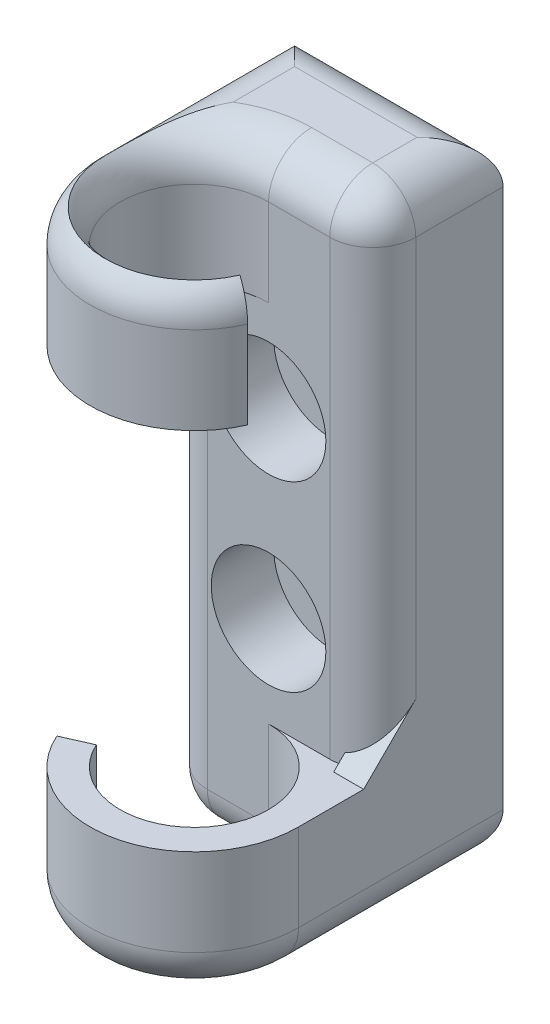
SolidWorks part; units mm, degrees
ref_plane "Front Plane" through (0, 0, 0) normal (1, 0, 0) x (0, 1, 0)
ref_plane "Top Plane" through (0, 0, 0) normal (0, 0, 1) x (0, 1, 0)
ref_plane "Right Plane" through (0, 0, 0) normal (0, 1, 0) x (-1, 0, 0)
sketch "Sketch1" plane through (0, 0, 0) normal (0, 0, 1) x (0, 1, 0)
  line L0 (-10, 0) -> (-12, 0) construction
  line L1 (-10, 2.35) -> (10, 2.35)
  line L2 (-10, 2.35) -> (-10, -2.35)
  line L3 (-10, -2.35) -> (10, -2.35)
  line L4 (10, 2.35) -> (10, -2.35)
  line L5 (-10, 2.35) -> (10, -2.35) construction
  line L6 (-10, -2.35) -> (10, 2.35) construction
  line L7 (-12, 4) -> (12, 4)
  line L8 (-12, 4) -> (-12, -4)
  line L9 (-12, -4) -> (12, -4)
  line L10 (12, 4) -> (12, -4)
  line L11 (0, 2.35) -> (0, 4) construction
  point P0 (0, 0)
  dimension "D1" = 4.7
  dimension "D2" = 20
  dimension "D3" = 2
  dimension "D4" = 8
extrude "Base" add sketch "Sketch1" along normal blind 5 contours L4 L1 L2 L3 | L10 L7 L8 L9 L1 L4 L3 L2 region at (0, 0, 0) region at (-3.747, 0, 0)
sketch "Hook Path" plane through (0, 12, 0) normal (0, 1, 0) x (-1, 0, 0)
  line L0 (2.85, 5) -> (2.85, 7.85)
  line L1 (4, 5) -> (-4, 5) construction
  line L2 (2.85, 7.85) -> (0, 7.85) construction
  line L3 (0, 5) -> (0, 7.85) construction
  line L4 (4, 5) -> (4, 0) construction
  arc A0 (2.85, 7.85) -> (-2.6077, 9) centre (0, 7.85) ccw
  circle A3 centre (0, 7.35) radius 2.35 construction
  point P6 (0, 10.7)
  point P11 (0, 9.7)
  dimension "D2" = 2.85
  dimension "D5" = 1.15
  dimension "D6" = 1
  dimension "D4" = 4.7
  dimension "D1" = 2.85
  dimension "D3" = 4
sketch "Sketch - Hook Base" plane through (0, 0, 5) normal (0, 0, 1) x (1, 0, 0)
  line L1 (-4, 12) -> (-2.85, 12)
  line L2 (-4, 12) -> (-4, 7)
  line L3 (-4, 7) -> (-2.85, 7)
  line L4 (-2.85, 12) -> (-2.85, 7)
  line L5 (-4, 12) -> (4, 12) construction
  line L6 (-4, -12) -> (-4, 12) construction
  dimension "D1" = 1.15
  dimension "D2" = 5
fillet "Base-Fillet" radius 1.65 2 edges at (4, 0, 5) (-4, 0, 5)
extrude "Hook Base" add sketch "Sketch - Hook Base" against normal up to surface (5 mm away) contours L3 L4 L1 L2 up to face at (0, 0, 0)
sweep "Hook" add profiles "Sketch - Hook Base<3>" path "Hook Path"
sketch "Sketch - Hook Base<3>" plane through (0, 0, 5) normal (0, 0, 1) x (1, 0, 0) same geometry as "Sketch - Hook Base"
ref_plane "Plane - Hook Rib" through (-3.425, 0, 0) normal (1, 0, 0) x (0, 1, 0)
ref_point "Top Face Midpoint"
ref_axis "Axis - Top Face Midpoint" through (0, 0, 5) along (0, 0, 1)
sketch "Sketch10" plane through (0, 0, 5) normal (0, 0, 1) x (1, 0, 0)
  line L0 (0, 3.5) -> (0, -3.5) construction
  line L1 (-2.35, 12) -> (-2.35, -12) construction
  point P6 (0, 3.5)
  point P7 (0, -3.5)
  dimension "D1" = 7
hole_wizard "CBORE for M2 Hex Socket Head Cap Screw1" positions "Sketch11" profile "Sketch13" counterbore size "M2" standard "ISO"
sketch "Sketch11" plane through (0, 0, 5) normal (0, 0, 1) x (0, -1, 0)
  point P0 (3.5, 0)
  point P3 (-3.5, 0)
sketch "Sketch13" plane through (0, -3.5, 5) normal (1, 0, 0) x (0, -1, 0)
  line L0 (0, 0) -> (0, 7.971)
  line L1 (0, 7.971) -> (1.2, 7.25)
  line L2 (1.2, 7.25) -> (1.2, 2.4)
  line L3 (1.2, 2.4) -> (2.2, 2.4)
  line L4 (2.2, 2.4) -> (2.2, 0)
  line L5 (2.2, 0) -> (0, 0)
  line L10 (0, 7.971) -> (-1.2, 7.25) construction
  line L11 (0, -6.35) -> (0, 107.95) construction
  dimension "Hole Dia." = 2.4
  dimension "Hole Depth" = 7.25
  dimension "C'Bore Dia." = 4.4
  dimension "C'Bore Depth" = 2.4
  dimension "Drill Angle" = 118
sketch "Sketch16" plane through (0, 0, 0) normal (1, 0, 0) x (0, 1, 0)
  line L0 (7, 4.9224) -> (7, 7.85) construction
  line L1 (7, 5) -> (12, 5)
  line L2 (7, 5) -> (7, 3.35)
  line L3 (7, 3.35) -> (12, 3.35)
  line L4 (12, 5) -> (12, 3.35)
  point P4 (0, 0)
  point P5 (0, 0)
  point P6 (0, 0)
  point P7 (7.0678, 5)
  point P9 (12, 4.8339)
  point P11 (0, 0)
  point P14 (12, 3.458)
  point P15 (0, 0)
  point P17 (0, 0)
sketch "Sketch15" plane through (0, 12, 0) normal (0, 1, 0) x (-1, 0, 0)
  line L1 (2.85, 4.9224) -> (2.85, 7.85) construction
  line L2 (2.35, 5) -> (-2.35, 5) construction
  arc A0 (0, 5) -> (2.85, 7.85) centre (0, 7.85) ccw
  arc A1 (2.85, 7.85) -> (-2.6077, 9) centre (0, 7.85) ccw construction
  point P5 (0, 0)
  point P8 (2.097, 5)
  point P9 (-0.0103, 7.8603)
  point P13 (0, 0)
sweep "Sweep1" add profiles "Sketch16" path "Sketch15"
sketch "Sketch6" plane through (0, 7, 0) normal (0, -1, 0) x (1, 0, 0)
  line L0 (-4, 5) -> (-2.85, 5) construction
  line L1 (-4, 5) -> (-2.85, 5) construction
  line L3 (-2.85, 7.85) -> (-4, 7.85) construction
  line L4 (-3.425, 7.85) -> (-3.425, 5) construction
  line L10 (-4, 5.35) -> (-2.85, 5.35)
  line L11 (-4, 5.35) -> (-4, 3.35)
  line L12 (-4, 3.35) -> (-2.85, 3.35)
  line L13 (-2.85, 5.35) -> (-2.85, 3.35)
  arc A2 (2.6077, 9) -> (0, 5) centre (0, 7.85) ccw construction
  arc A3 (3.6599, 9.464) -> (-4, 7.85) centre (0, 7.85) ccw construction
  point P8 (-3.425, 6.425)
  point P12 (-3.425, 5.35)
  point P14 (0, 0)
  point P22 (0, 0)
  point P23 (0, 0)
  point P24 (-3.425, 7.85)
  point P25 (-3.425, 5)
  point P27 (0, 7.85)
  dimension "D2" = 2
sketch "Sketch8" plane through (-3.425, 0, 0) normal (1, 0, 0) x (0, 1, 0)
  line L1 (12, 3.35) -> (-12, 3.35) construction
  line L5 (7, 7.85) -> (7, 5) construction
  line L6 (7, 5.35) -> (5, 3.35)
  point P0 (7, 5.35)
  dimension "D1" = 45
sweep "Sweep - Hook Rib" add profiles "Sketch6" path "Sketch8"
sketch "Sketch19" plane through (0, 0, 7.85) normal (0, 0, 1) x (1, 0, 0)
  line L4 (-4, 7) -> (-4, 12)
  line L5 (-4, 12) -> (-4.5, 12)
  line L6 (-4.5, 12) -> (-4.5, 7)
  line L7 (-4.5, 7) -> (-4, 7)
  line L8 (-4, 7) -> (-4, 12)
  line L9 (-4, 12) -> (-4.5, 12)
  line L10 (-4.5, 12) -> (-4.5, 7)
  line L11 (-4.5, 7) -> (-4, 7)
  dimension "D1" = 0
extrude "Cut-Extrude4" cut sketch "Sketch19" against normal up to surface (7.85 mm away) up to face at (1.2, -3.5, 0)
pattern_circular "CirPattern1" count 2 every 180 about axis through (0, 0, 5) along (0, 0, 1) of "Hook Base", "Hook", "Sweep - Hook Rib", "Cut-Extrude4", "Sweep1"
fillet "Fillet1" radius 1.65 16 edges at (-4, -12, 1.675) (-3.1338, -12, 9.232) (2.3875, -12, 9.4064) (0.8247, -12, 11.7641) (4, 12, 1.675) (3.5167, 12, 4.5167) (4, -12, 3.925) (-1.175, -12, 5) (-3.5167, -12, 4.5167) (3.1338, 12, 9.232) (-2.3875, 12, 9.4064) (-0.8247, 12, 11.7641) (0, -12, 0) (0, 12, 0) (1.175, 12, 5) (-4, 12, 3.925)
